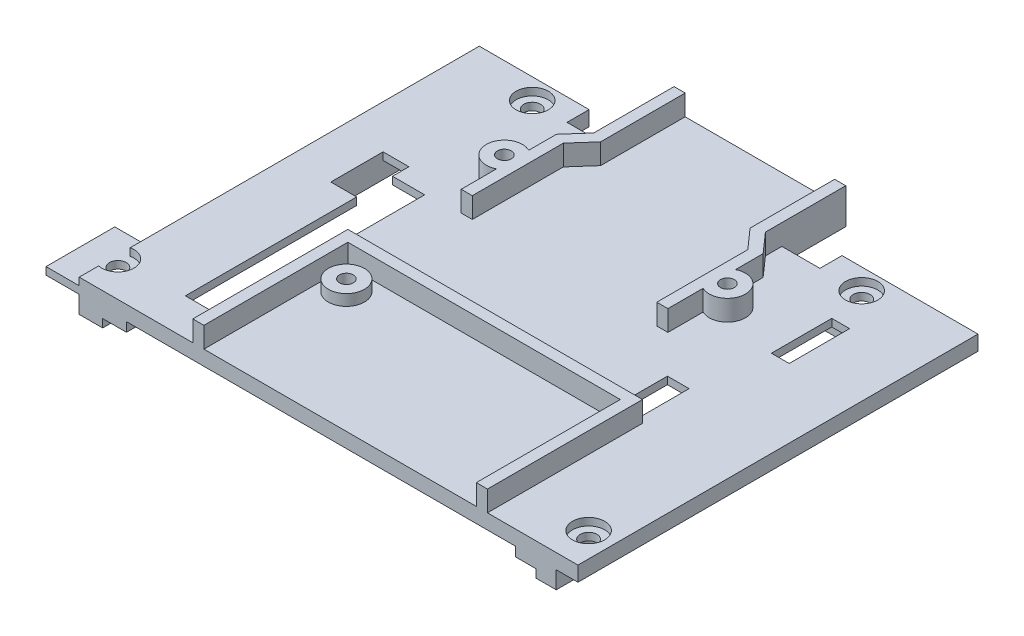
SolidWorks part; units mm, degrees
ref_plane "Front Plane" through (0, 0, 0) normal (0, 0, 1) x (1, 0, 0)
ref_plane "Top Plane" through (0, 0, 0) normal (0, 1, 0) x (1, 0, 0)
ref_plane "Right Plane" through (0, 0, 0) normal (1, 0, 0) x (0, 0, -1)
sketch "Sketch1" plane through (0, 0, 0) normal (0, 1, 0) x (1, 0, 0)
  line L0 (59.1034, 32.478) -> (59.1034, -39.482)
  line L1 (-22.7866, 23.578) -> (48.5034, 23.578)
  line L2 (-22.7866, 23.578) -> (-22.7866, -35.642)
  line L3 (-22.7866, -35.642) -> (48.5034, -35.642)
  line L4 (48.5034, 23.578) -> (48.5034, -35.642)
  line L5 (59.1034, -39.482) -> (-36.5666, -39.482)
  line L6 (-36.5666, -39.482) -> (-36.5666, -27.112)
  line L7 (-36.5666, -27.112) -> (-30.5966, -27.112)
  line L8 (-30.5966, -27.112) -> (-30.5966, 32.478)
  line L9 (-30.5966, 32.478) -> (-10.8366, 32.478)
  line L10 (-10.8366, 32.478) -> (-10.8366, 28.498)
  line L11 (-10.8366, 28.498) -> (34.6434, 28.498)
  line L12 (34.6434, 28.498) -> (34.6434, 32.478)
  line L13 (34.6434, 32.478) -> (59.1034, 32.478)
  line L15 (-30.5966, 28.498) -> (55.2034, 28.498)
  line L16 (-30.5966, 28.498) -> (-30.5966, -39.482)
  line L17 (-30.5966, -39.482) -> (55.2034, -39.482)
  line L18 (55.2034, 28.498) -> (55.2034, -39.482)
  line L19 (-22.0866, -35.642) -> (47.8834, -35.642)
  line L20 (-22.0866, -35.642) -> (-22.0866, -39.482)
  line L21 (-22.0866, -39.482) -> (47.8834, -39.482)
  line L22 (47.8834, -35.642) -> (47.8834, -39.482)
  line L23 (-26.3766, -39.482) -> (51.5534, -39.482)
  line L24 (-26.3766, -39.482) -> (-26.3766, 26.298)
  line L25 (-26.3766, 26.298) -> (51.5534, 26.298)
  line L26 (51.5534, -39.482) -> (51.5534, 26.298)
  circle A0 centre (-17.3716, 28.773) radius 1.515
  circle A1 centre (41.8884, 28.773) radius 1.515
  circle A2 centre (54.6884, -33.147) radius 1.515
  circle A3 centre (-29.9716, -33.147) radius 1.515
  circle A4 centre (-17.3716, 28.773) radius 2.9
  circle A5 centre (41.8884, 28.773) radius 2.9
  circle A6 centre (54.6884, -33.147) radius 2.9
  circle A7 centre (-29.9716, -33.147) radius 2.9
  dimension "D12" = 3.03
  dimension "D13" = 3.03
  dimension "D14" = 3.03
  dimension "D15" = 3.03
  dimension "D22" = 5.8
  dimension "D23" = 5.8
  dimension "D24" = 5.8
  dimension "D25" = 5.8
  dimension "D1" = 71.29
  dimension "D2" = 59.22
  dimension "D3" = 3.84
  dimension "D4" = 10.6
  dimension "D5" = 13.78
  dimension "D6" = 7.81
  dimension "D7" = 12.37
  dimension "D8" = 4.92
  dimension "D9" = 8.9
  dimension "D10" = 19.76
  dimension "D11" = 24.46
  dimension "D16" = 59.26
  dimension "D17" = 3.705
  dimension "D18" = 13.225
  dimension "D19" = 84.66
  dimension "D20" = 6.335
  dimension "D21" = 6.595
  dimension "D26" = 3.9
  dimension "D27" = 14.48
  dimension "D28" = 11.22
  dimension "D29" = 3.65
  dimension "D30" = 2.2
  dimension "D31" = 4.22
extrude "Boss-Extrude1" add sketch "Sketch1" against normal blind 1.34 contours A4 L15 L10 L9 L8 | L15 A4 A0 | A6 L18 L5 L0 L13 L12 L15 A5 | L15 A5 A1 | L18 A6 A2 | L22 L3 L20 L17 | A7 L16 L7 L6 L5 | L16 A7 A3 | L25 A4 L15 A0 | L25 A5 L15 A1 | L25 A5 | L25 A4 | L16 A7 A3 | L18 A6 A2 region at (58.3434, 0, 3.502) region at (51.8557, 0, 33.147) region at (56.3504, 0, 33.147) region at (-21.4922, 0, -30.6344) region at (41.7539, 0, -31.6037) region at (39.7, 0, -28.4363) region at (12.8984, 0, 37.562) region at (-14.965, 0, -27.2684) region at (-15.1832, 0, -28.5642) region at (41.8884, 0, -26.1269) region at (-17.3716, 0, -26.1269) region at (-33.8862, 0, 33.3194) region at (-31.6777, 0, 33.147) region at (-30.5287, 0, 35.2529)
extrude "Boss-Extrude2" add sketch "Sketch1<4>" against normal blind 3 contours A5 L25 A4 L24 L17 L20 L3 L2 L1 L4 L22 L26 region at (49.7184, 0, 38.4621)
sketch "Sketch1<4>" plane through (0, 0, 0) normal (0, 1, 0) x (1, 0, 0) same geometry as "Sketch1"
extrude "Boss-Extrude3" add sketch "Sketch1<6>" against normal blind 4.47 contours A7 L16 L5 L24 L25 A4 L15 L8 | A5 L15 L11 A4 L25 | A6 L18 L15 A5 L25 L26 L5 region at (53.0062, 0, 1.5798) region at (12.2584, 0, -27.3894) region at (-28.1779, 0, 2.1911)
sketch "Sketch1<6>" plane through (0, 0, 0) normal (0, 1, 0) x (1, 0, 0) same geometry as "Sketch1"
sketch "Sketch2" plane through (0, 0, 0) normal (0, 1, 0) x (1, 0, 0)
  line L0 (-22.7866, 23.578) -> (-22.7866, -35.642) construction
  line L1 (-30.5966, 32.478) -> (59.1034, 32.478)
  line L2 (-30.5966, 32.478) -> (-30.5966, -39.482)
  line L3 (-30.5966, -39.482) -> (59.1034, -39.482)
  line L4 (59.1034, 32.478) -> (59.1034, -39.482)
  line L5 (43.5034, 21.778) -> (46.7034, 21.778)
  line L6 (43.5034, 21.778) -> (43.5034, 10.918)
  line L7 (43.5034, 10.918) -> (46.7034, 10.918)
  line L8 (46.7034, 21.778) -> (46.7034, 10.918)
  line L9 (37.7234, -2.002) -> (41.6234, -2.002)
  line L10 (37.7234, -2.002) -> (37.7234, -11.592)
  line L11 (37.7234, -11.592) -> (41.6234, -11.592)
  line L12 (41.6234, -2.002) -> (41.6234, -11.592)
  line L13 (-22.7866, 7.368) -> (-18.1366, 7.368)
  line L14 (-22.7866, 7.368) -> (-22.7866, -2.042)
  line L15 (-22.7866, -2.042) -> (-18.1366, -2.042)
  line L16 (-18.1366, 7.368) -> (-18.1366, -2.042)
  line L17 (48.5034, 23.578) -> (48.5034, -35.642) construction
  line L18 (-18.1366, 4.408) -> (-12.3566, 4.408)
  line L19 (-18.1366, 4.408) -> (-18.1366, -32.842)
  line L20 (-18.1366, -32.842) -> (-12.3566, -32.842)
  line L21 (-12.3566, 4.408) -> (-12.3566, -32.842)
  line L22 (-22.7866, 23.578) -> (48.5034, 23.578) construction
  line L23 (-22.7866, -35.642) -> (48.5034, -35.642) construction
  line M13 (34.6434, 28.498) -> (-10.8366, 28.498)
  line M14 (-10.8366, 28.498) -> (-10.8366, 32.478)
  line M15 (-10.8366, 32.478) -> (-30.5966, 32.478)
  line M16 (-30.5966, 32.478) -> (-30.5966, -27.112)
  line M19 (-36.5666, -39.482) -> (59.1034, -39.482)
  line M20 (59.1034, -39.482) -> (59.1034, 32.478)
  line M21 (59.1034, 32.478) -> (34.6434, 32.478)
  line M22 (34.6434, 32.478) -> (34.6434, 28.498)
  circle M23 centre (-17.3716, 28.773) radius 1.515
  circle M24 centre (-29.9716, -33.147) radius 1.515
  line M25 (48.5034, 23.578) -> (48.5034, -35.642)
  line M26 (48.5034, -35.642) -> (-22.7866, -35.642)
  line M27 (-22.7866, -35.642) -> (-22.7866, 23.578)
  line M28 (-22.7866, 23.578) -> (48.5034, 23.578)
  circle M29 centre (54.6884, -33.147) radius 1.515
  circle M30 centre (41.8884, 28.773) radius 1.515
  dimension "D1" = 3.2
  dimension "D2" = 10.86
  dimension "D3" = 1.8
  dimension "D4" = 1.8
  dimension "D5" = 25.58
  dimension "D6" = 24.05
  dimension "D7" = 6.88
  dimension "D8" = 10.78
  dimension "D9" = 4.65
  dimension "D10" = 16.21
  dimension "D11" = 33.6
  dimension "D12" = 19.17
  dimension "D13" = 2.8
  dimension "D14" = 10.43
extrude "Boss-Extrude4" add sketch "Sketch2" along normal blind 1.34 contours L18 L21 L20 L19 L15 L13 L16 L5 L8 L7 L6 L9 L12 L11 L10 M27 M26 M25 M28 | L2 M16 M24 M19 M20 M21 M22 M13 M14 M15 M23 M28 M25 M26 M27 M29 M30 region at (-20.7166, 0, -31.3281) region at (14.2427, 0, 5.8693)
extrude "Cut-Extrude1" cut sketch "Sketch1<8>" along normal through all from surface contours L16 A7 A3 | L18 A6 A2 | L18 A6 A2 | L15 A5 A1 | L25 A5 L15 A1 | L25 A5 | L15 A4 A0 | L25 A4 L15 A0 | L25 A4 region at (51.8557, 0, 33.147) region at (56.3504, 0, 33.147) region at (41.7539, 0, -31.6037) region at (39.7, 0, -28.4363) region at (-14.965, 0, -27.2684) region at (-15.1832, 0, -28.5642) region at (41.8884, 0, -26.1269) region at (-17.3716, 0, -26.1269) region at (-30.5287, 0, 35.2529) starting at face at (-32.7349, 0, 33.247)
sketch "Sketch1<8>" plane through (0, 0, 0) normal (0, 1, 0) x (1, 0, 0) same geometry as "Sketch1"
sketch "Sketch3" plane through (0, 1.34, 0) normal (0, 1, 0) x (1, 0, 0)
  line L0 (-1.0723, 39.988) -> (-1.0723, 24.778)
  line L1 (-1.0723, 24.778) -> (-4.2223, 21.218)
  line L2 (-4.2223, 21.218) -> (-4.2223, 6.848)
  line L3 (-4.2223, 6.848) -> (28.9577, 6.848)
  line L4 (28.9577, 6.848) -> (28.9577, 21.218)
  line L5 (28.9577, 21.218) -> (25.8077, 24.778)
  line L6 (25.8077, 24.778) -> (25.8077, 29.8534)
  line L7 (25.8077, 29.8534) -> (25.8077, 39.988)
  line L8 (25.8077, 39.988) -> (-1.0723, 39.988)
  line L9 (34.6434, 28.498) -> (-10.8366, 28.498) construction
  line L10 (-3.0723, 41.988) -> (-3.0723, 25.5358)
  line L11 (-3.0723, 25.5358) -> (-6.2223, 21.9758)
  line L12 (-6.2223, 21.9758) -> (-6.2223, 4.848)
  line L13 (-6.2223, 4.848) -> (30.9577, 4.848)
  line L14 (30.9577, 4.848) -> (30.9577, 21.9758)
  line L15 (30.9577, 21.9758) -> (27.8077, 25.5358)
  line L16 (27.8077, 25.5358) -> (27.8077, 29.8534)
  line L17 (27.8077, 29.8534) -> (27.8077, 41.988)
  line L18 (27.8077, 41.988) -> (-3.0723, 41.988)
  line L19 (-4.2223, 6.848) -> (-4.2223, 4.848)
  line L20 (28.9577, 6.848) -> (28.9577, 4.848)
  line L21 (-1.0723, 39.988) -> (-3.0723, 39.988)
  line L22 (25.8077, 39.988) -> (27.8077, 39.988)
  line L23 (-30.5966, 32.478) -> (-30.5966, -30.3151) construction
  line M34 (34.6434, 28.498) -> (-10.8366, 28.498)
  dimension "D1" = 26.88
  dimension "D2" = 33.18
  dimension "D3" = 14.37
  dimension "D4" = 3.15
  dimension "D5" = 15.21
  dimension "D6" = 33.14
  dimension "D7" = 11.49
  dimension "D9" = 24.3743
  dimension "D8" = 2
extrude "Boss-Extrude5" add sketch "Sketch3" against normal up to surface (2.68 mm away) contours L0 L21 L10 M34 | L7 L8 L0 M34 | L22 L7 L17 M34 region at (12.3677, 1.34, -34.243) region at (-2.0723, 1.34, -34.243) region at (26.8077, 1.34, -34.243) up to face at (48.8669, -1.34, -3.1065)
extrude "Boss-Extrude6" add sketch "Sketch3<5>" along normal blind 3.71 contours L4 L20 L13 L14 L15 L16 L17 L7 L6 L5 M34 | L22 L7 L17 M34 | L19 L2 L1 L0 L10 L11 L12 L13 M34 | L0 L21 L10 M34 region at (-2.0723, 1.34, -34.243) region at (-4.4973, 1.34, -16.9951) region at (26.8077, 1.34, -34.243) region at (29.2327, 1.34, -16.9951)
sketch "Sketch3<5>" plane through (0, 1.34, 0) normal (0, 1, 0) x (1, 0, 0) same geometry as "Sketch3"
sketch "Sketch4" plane through (0, 1.34, 0) normal (0, 1, 0) x (1, 0, 0)
  circle A0 centre (-7.6991, 14.0959) radius 1.25
  circle A1 centre (32.4099, 14.0959) radius 1.25
  circle A2 centre (-7.6991, 14.0959) radius 3.25
  circle A3 centre (32.4099, 14.0959) radius 3.25
  dimension "D1" = 2.5
  dimension "D3" = 40.109
  dimension "D2" = 2
extrude "Boss-Extrude7" add sketch "Sketch4" along normal up to surface (3.71 mm away) up to face at (-3.6473, 5.05, -22.8975)
extrude "Cut-Extrude2" cut sketch "Sketch4<2>" against normal through all contours A0 | A1 region at (-7.6991, 1.34, -14.0959) region at (32.4099, 1.34, -14.0959)
sketch "Sketch4<2>" plane through (0, 1.34, 0) normal (0, 1, 0) x (1, 0, 0) same geometry as "Sketch4"
sketch "Sketch5" plane through (0, 1.34, 0) normal (0, 1, 0) x (1, 0, 0)
  line L0 (-30.5966, 32.478) -> (-30.5966, -30.3151) construction
  line L1 (-8.1666, -13.592) -> (40.8334, -13.592)
  line L2 (-8.1666, -13.592) -> (-8.1666, -48.702)
  line L3 (-8.1666, -48.702) -> (40.8334, -48.702)
  line L4 (40.8334, -13.592) -> (40.8334, -48.702)
  line L5 (37.7234, -11.592) -> (41.6234, -11.592) construction
  line L6 (-10.1666, -11.592) -> (42.8334, -11.592)
  line L7 (42.8334, -11.592) -> (42.8334, -50.702)
  line L8 (-10.1666, -50.702) -> (42.8334, -50.702)
  line L9 (-10.1666, -11.592) -> (-10.1666, -50.702)
  circle A0 centre (-4.3016, -17.717) radius 1.25
  circle A1 centre (-4.3016, -17.717) radius 3.25
  line M28 (-30.5966, -39.482) -> (59.1034, -39.482)
  line M38 (41.6234, -11.592) -> (37.7234, -11.592)
  dimension "D6" = 2.5
  dimension "D1" = 22.43
  dimension "D2" = 2
  dimension "D3" = 49
  dimension "D4" = 35.11
  dimension "D8" = 3.865
  dimension "D9" = 4.125
  dimension "D5" = 2
  dimension "D7" = 2
extrude "Boss-Extrude8" add sketch "Sketch5" along normal up to surface (3.71 mm away) contours L6 L9 L2 L1 L4 L7 M28 M38 region at (-8.7655, 1.34, 26.537) up to face at (-4.635, 5.05, -21.1372)
extrude "Cut-Extrude3" cut sketch "Sketch5<3>" against normal through all contours A0 region at (-4.3016, 1.34, 17.717)
sketch "Sketch5<3>" plane through (0, 1.34, 0) normal (0, 1, 0) x (1, 0, 0) same geometry as "Sketch5"
extrude "Boss-Extrude9" add sketch "Sketch5<4>" along normal blind 2 contours A1 A0 region at (-7.4597, 1.34, 17.717)
sketch "Sketch5<4>" plane through (0, 1.34, 0) normal (0, 1, 0) x (1, 0, 0) same geometry as "Sketch5"
